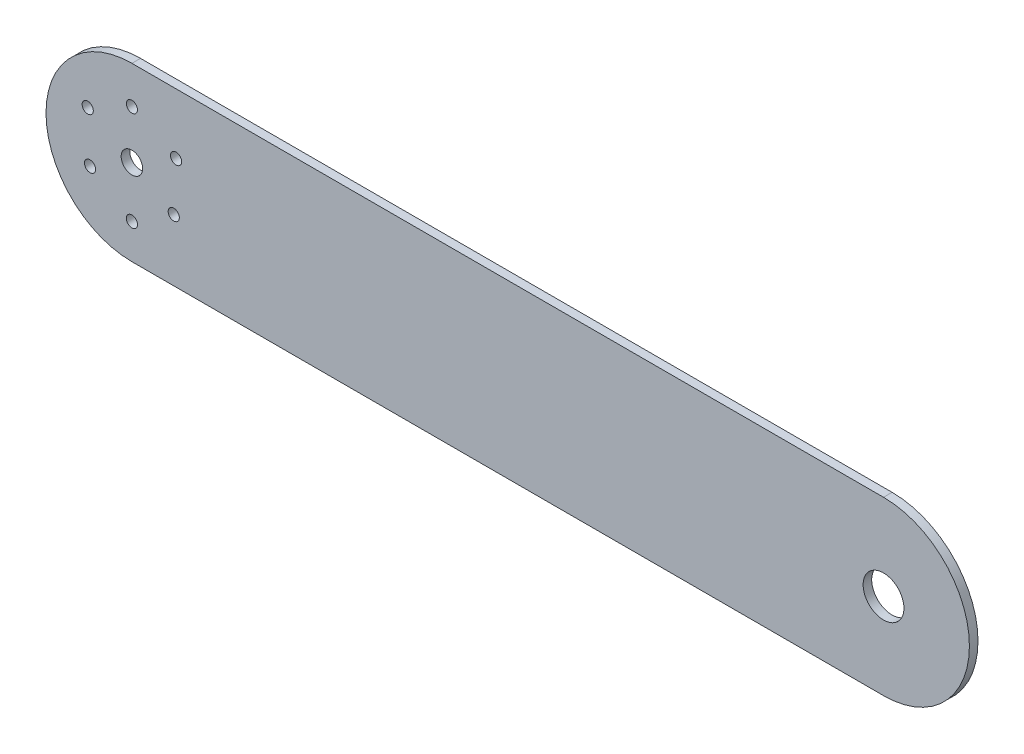
SolidWorks part; units mm, degrees
ref_plane "前视基准面" through (0, 0, 0) normal (0, 0, 1) x (1, 0, 0)
ref_plane "上视基准面" through (0, 0, 0) normal (0, 1, 0) x (1, 0, 0)
ref_plane "右视基准面" through (0, 0, 0) normal (1, 0, 0) x (0, 0, -1)
sketch "草图1" plane through (0, 0, 0) normal (0, 0, 1) x (1, 0, 0)
  line L0 (-1.4571, -0.1457) -> (37.8152, -22.8196) construction
  line L1 (-1.4571, -0.1457) -> (348.5429, -0.1457) construction
  line L2 (-1.4571, 39.8543) -> (348.5429, 39.8543)
  line L3 (-1.4571, -40.1457) -> (348.5429, -40.1457)
  circle A0 centre (-1.4571, -0.1457) radius 23.75 construction
  circle A1 centre (-1.4571, -0.1457) radius 22.5 construction
  circle A2 centre (-1.4571, -23.8957) radius 2.6
  circle A3 centre (18.0284, -11.3957) radius 2.6
  circle A4 centre (-1.4571, -0.1457) radius 40 construction
  arc A5 (-1.4571, 39.8543) -> (-1.4571, -40.1457) centre (-1.4571, -0.1457) ccw
  circle A6 centre (-1.4571, -0.1457) radius 5
  circle A7 centre (-22.0252, 11.7293) radius 2.6
  circle A8 centre (19.111, 11.7293) radius 2.6
  circle A9 centre (-20.9427, -11.3957) radius 2.6
  circle A10 centre (-1.4571, 22.3543) radius 2.6
  circle A11 centre (348.5429, -0.1457) radius 9.5
  circle A12 centre (348.5429, -0.1457) radius 40 construction
  arc A13 (348.5429, 39.8543) -> (348.5429, -40.1457) centre (348.5429, -0.1457) cw
  dimension "D1" = 45
  dimension "D2" = 5.2
  dimension "D3" = 5.2
  dimension "D4" = 19
  dimension "D5" = 80
  dimension "D6" = 80
extrude "凸台-拉伸1" add sketch "草图1" along normal blind 4
